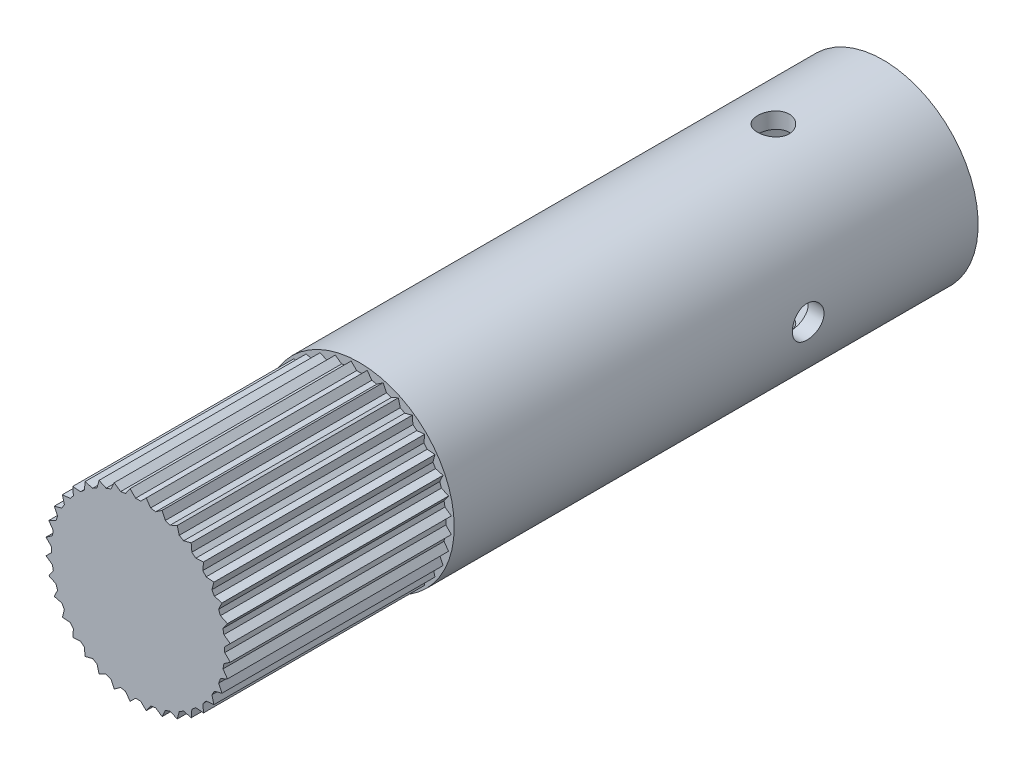
SolidWorks part; units mm, degrees
material "AISI 4130 Steel, annealed at 865C"
ref_plane "X-Y Datum" through (0, 0, 0) normal (0, 0, 1) x (1, 0, 0)
ref_plane "X-Z Datum" through (0, 0, 0) normal (0, 1, 0) x (1, 0, 0)
ref_plane "Y-Z Datum" through (0, 0, 0) normal (1, 0, 0) x (0, 0, -1)
sketch "Sketch9" plane through (0, 0, 0) normal (0, 1, 0) x (1, 0, 0)
  line L0 (16.002, 0) -> (0, 0)
  line L1 (0, 0) -> (0, -389.0916)
  line L2 (0, -389.0916) -> (-72.2493, -524.9728)
  dimension "D1" = 153.895
  dimension "D2" = 28
  dimension "D3" = 389.0916
  dimension "D5" = 16.002
sketch "Sketch5" plane through (0, 0, 0) normal (0, 1, 0) x (1, 0, 0)
  line L0 (7.9375, -96.8417) -> (7.9375, -22.1615)
  line L1 (7.9375, -22.1615) -> (9.525, -22.1615)
  line L2 (9.525, -22.1615) -> (9.525, -96.8417)
  line L3 (9.525, -96.8417) -> (7.9375, -96.8417)
  line L5 (16.002, 0) -> (0, 0) construction
  line L6 (0, 0) -> (0, -389.0916) construction
  line L7 (0, -389.0916) -> (9.525, -389.0916) construction
  line L8 (12.5602, -58.6916) -> (0, -58.6916) construction
  dimension "D1" = 1.5875
  dimension "D2" = 22.1615
  dimension "D3" = 7.9375
  dimension "D4" = 330.4
  dimension "D5" = 292.2499
revolve "Revolve2" add sketch "Sketch5" angle 360 about L1
sketch "Sketch6" plane through (0, 0, 0) normal (0, 1, 0) x (1, 0, 0)
  circle A0 centre (0, -33.1635) radius 1.5875 construction
  circle A1 centre (0, -33.1635) radius 1.5875
sketch "Sketch7" plane through (0, 0, 0) normal (1, 0, 0) x (0, 0, -1)
  circle A2 centre (-39.196, 0) radius 1.5875
  circle A4 centre (-39.196, 0) radius 1.5875 construction
extrude "Cut-Extrude5" cut sketch "Sketch7" against normal through all both and the other way through all
extrude "Cut-Extrude6" cut sketch "Sketch6" against normal through all both and the other way through all
sketch "Sketch8" plane through (0, 0, 0) normal (0, 0, 1) x (1, 0, 0)
  line L0 (9.2357, -0.808) -> (8.6817, -0.254)
  line L1 (8.6817, -0.254) -> (8.6817, 0.254)
  line L2 (8.6817, 0.254) -> (9.2357, 0.808)
  line L3 (8.6817, 0) -> (0, 0) construction
  line L4 (8.9551, -2.3995) -> (8.5057, -1.7577)
  line L5 (8.5057, -1.7577) -> (8.5939, -1.2574)
  line L6 (8.5939, -1.2574) -> (9.2357, -0.808)
  line L7 (8.4024, -3.9181) -> (8.0713, -3.208)
  line L8 (8.0713, -3.208) -> (8.245, -2.7306)
  line L9 (8.245, -2.7306) -> (8.9551, -2.3995)
  line L10 (7.5944, -5.3176) -> (7.3916, -4.5608)
  line L11 (7.3916, -4.5608) -> (7.6456, -4.1209)
  line L12 (7.6456, -4.1209) -> (8.4024, -3.9181)
  line L13 (6.5556, -6.5556) -> (6.4873, -5.7751)
  line L14 (6.4873, -5.7751) -> (6.8138, -5.3859)
  line L15 (6.8138, -5.3859) -> (7.5944, -5.3176)
  line L16 (5.3176, -7.5944) -> (5.3859, -6.8138)
  line L17 (5.3859, -6.8138) -> (5.7751, -6.4873)
  line L18 (5.7751, -6.4873) -> (6.5556, -6.5556)
  line L19 (3.9181, -8.4024) -> (4.1209, -7.6456)
  line L20 (4.1209, -7.6456) -> (4.5608, -7.3916)
  line L21 (4.5608, -7.3916) -> (5.3176, -7.5944)
  line L22 (2.3995, -8.9551) -> (2.7306, -8.245)
  line L23 (2.7306, -8.245) -> (3.208, -8.0713)
  line L24 (3.208, -8.0713) -> (3.9181, -8.4024)
  line L25 (0.808, -9.2357) -> (1.2574, -8.5939)
  line L26 (1.2574, -8.5939) -> (1.7577, -8.5057)
  line L27 (1.7577, -8.5057) -> (2.3995, -8.9551)
  line L28 (-0.808, -9.2357) -> (-0.254, -8.6817)
  line L29 (-0.254, -8.6817) -> (0.254, -8.6817)
  line L30 (0.254, -8.6817) -> (0.808, -9.2357)
  line L31 (-2.3995, -8.9551) -> (-1.7577, -8.5057)
  line L32 (-1.7577, -8.5057) -> (-1.2574, -8.5939)
  line L33 (-1.2574, -8.5939) -> (-0.808, -9.2357)
  line L34 (-3.9181, -8.4024) -> (-3.208, -8.0713)
  line L35 (-3.208, -8.0713) -> (-2.7306, -8.245)
  line L36 (-2.7306, -8.245) -> (-2.3995, -8.9551)
  line L37 (-5.3176, -7.5944) -> (-4.5608, -7.3916)
  line L38 (-4.5608, -7.3916) -> (-4.1209, -7.6456)
  line L39 (-4.1209, -7.6456) -> (-3.9181, -8.4024)
  line L40 (-6.5556, -6.5556) -> (-5.7751, -6.4873)
  line L41 (-5.7751, -6.4873) -> (-5.3859, -6.8138)
  line L42 (-5.3859, -6.8138) -> (-5.3176, -7.5944)
  line L43 (-7.5944, -5.3176) -> (-6.8138, -5.3859)
  line L44 (-6.8138, -5.3859) -> (-6.4873, -5.7751)
  line L45 (-6.4873, -5.7751) -> (-6.5556, -6.5556)
  line L46 (-8.4024, -3.9181) -> (-7.6456, -4.1209)
  line L47 (-7.6456, -4.1209) -> (-7.3916, -4.5608)
  line L48 (-7.3916, -4.5608) -> (-7.5944, -5.3176)
  line L49 (-8.9551, -2.3995) -> (-8.245, -2.7306)
  line L50 (-8.245, -2.7306) -> (-8.0713, -3.208)
  line L51 (-8.0713, -3.208) -> (-8.4024, -3.9181)
  line L52 (-9.2357, -0.808) -> (-8.5939, -1.2574)
  line L53 (-8.5939, -1.2574) -> (-8.5057, -1.7577)
  line L54 (-8.5057, -1.7577) -> (-8.9551, -2.3995)
  line L55 (-9.2357, 0.808) -> (-8.6817, 0.254)
  line L56 (-8.6817, 0.254) -> (-8.6817, -0.254)
  line L57 (-8.6817, -0.254) -> (-9.2357, -0.808)
  line L58 (-8.9551, 2.3995) -> (-8.5057, 1.7577)
  line L59 (-8.5057, 1.7577) -> (-8.5939, 1.2574)
  line L60 (-8.5939, 1.2574) -> (-9.2357, 0.808)
  line L61 (-8.4024, 3.9181) -> (-8.0713, 3.208)
  line L62 (-8.0713, 3.208) -> (-8.245, 2.7306)
  line L63 (-8.245, 2.7306) -> (-8.9551, 2.3995)
  line L64 (-7.5944, 5.3176) -> (-7.3916, 4.5608)
  line L65 (-7.3916, 4.5608) -> (-7.6456, 4.1209)
  line L66 (-7.6456, 4.1209) -> (-8.4024, 3.9181)
  line L67 (-6.5556, 6.5556) -> (-6.4873, 5.7751)
  line L68 (-6.4873, 5.7751) -> (-6.8138, 5.3859)
  line L69 (-6.8138, 5.3859) -> (-7.5944, 5.3176)
  line L70 (-5.3176, 7.5944) -> (-5.3859, 6.8138)
  line L71 (-5.3859, 6.8138) -> (-5.7751, 6.4873)
  line L72 (-5.7751, 6.4873) -> (-6.5556, 6.5556)
  line L73 (-3.9181, 8.4024) -> (-4.1209, 7.6456)
  line L74 (-4.1209, 7.6456) -> (-4.5608, 7.3916)
  line L75 (-4.5608, 7.3916) -> (-5.3176, 7.5944)
  line L76 (-2.3995, 8.9551) -> (-2.7306, 8.245)
  line L77 (-2.7306, 8.245) -> (-3.208, 8.0713)
  line L78 (-3.208, 8.0713) -> (-3.9181, 8.4024)
  line L79 (-0.808, 9.2357) -> (-1.2574, 8.5939)
  line L80 (-1.2574, 8.5939) -> (-1.7577, 8.5057)
  line L81 (-1.7577, 8.5057) -> (-2.3995, 8.9551)
  line L82 (0.808, 9.2357) -> (0.254, 8.6817)
  line L83 (0.254, 8.6817) -> (-0.254, 8.6817)
  line L84 (-0.254, 8.6817) -> (-0.808, 9.2357)
  line L85 (2.3995, 8.9551) -> (1.7577, 8.5057)
  line L86 (1.7577, 8.5057) -> (1.2574, 8.5939)
  line L87 (1.2574, 8.5939) -> (0.808, 9.2357)
  line L88 (3.9181, 8.4024) -> (3.208, 8.0713)
  line L89 (3.208, 8.0713) -> (2.7306, 8.245)
  line L90 (2.7306, 8.245) -> (2.3995, 8.9551)
  line L91 (5.3176, 7.5944) -> (4.5608, 7.3916)
  line L92 (4.5608, 7.3916) -> (4.1209, 7.6456)
  line L93 (4.1209, 7.6456) -> (3.9181, 8.4024)
  line L94 (6.5556, 6.5556) -> (5.7751, 6.4873)
  line L95 (5.7751, 6.4873) -> (5.3859, 6.8138)
  line L96 (5.3859, 6.8138) -> (5.3176, 7.5944)
  line L97 (7.5944, 5.3176) -> (6.8138, 5.3859)
  line L98 (6.8138, 5.3859) -> (6.4873, 5.7751)
  line L99 (6.4873, 5.7751) -> (6.5556, 6.5556)
  line L100 (8.4024, 3.9181) -> (7.6456, 4.1209)
  line L101 (7.6456, 4.1209) -> (7.3916, 4.5608)
  line L102 (7.3916, 4.5608) -> (7.5944, 5.3176)
  line L103 (8.9551, 2.3995) -> (8.245, 2.7306)
  line L104 (8.245, 2.7306) -> (8.0713, 3.208)
  line L105 (8.0713, 3.208) -> (8.4024, 3.9181)
  line L106 (9.2357, 0.808) -> (8.5939, 1.2574)
  line L107 (8.5939, 1.2574) -> (8.5057, 1.7577)
  line L108 (8.5057, 1.7577) -> (8.9551, 2.3995)
  circle A0 centre (0, 0) radius 12.7
  circle A1 centre (0, 0) radius 9.271 construction
  circle A2 centre (0, 0) radius 8.6854 construction
  point P153 (0, 0)
  dimension "D1" = 25.4
  dimension "D4" = 18.542
  dimension "D6" = 17.3708
  dimension "D2" = 0.508
  dimension "D3" = 135
  dimension "D5" = 36
ref_plane "Plane1" through (0, 0, 47.5615) normal (0, 0, -1) x (-1, 0, 0)
sketch "Sketch10" plane through (0, 0, 47.5615) normal (0, 0, -1) x (-1, 0, 0)
  circle A0 centre (0, 0) radius 7.9375
  dimension "D1" = 15.875
extrude "Boss-Extrude1" add sketch "Sketch10" against normal up to surface (49.2802 mm away) up to face at (-9.525, 0, 96.8417)
sketch "Sketch11" plane through (0, 0, 22.1615) normal (0, 0, -1) x (-1, 0, 0)
  line L0 (0, 9.525) -> (13.3548, 9.525) construction
  line L1 (0, 9.525) -> (0, 15.4312) construction
  line L2 (-9.525, 0) -> (-9.525, 9.1744) construction
  line L3 (-9.525, 0) -> (-16.674, 0) construction
  circle A0 centre (0, 0) radius 9.525 construction
  point P0 (0, 9.525)
  point P1 (-9.525, 0)
extrude "Cut-Extrude7" cut sketch "Sketch8" along normal blind 25.4 from offset 74.6811
